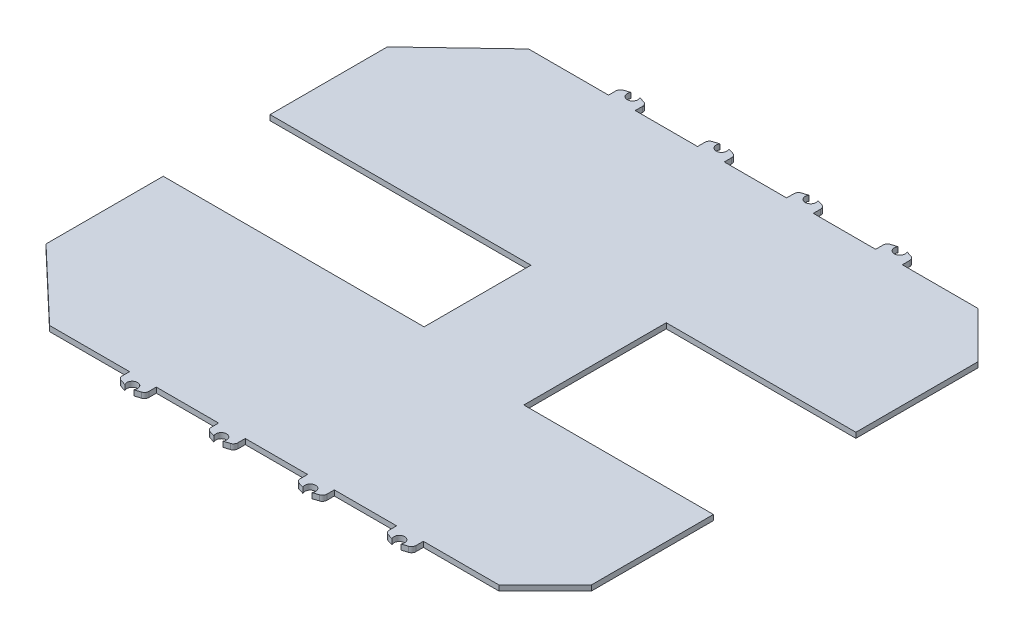
SolidWorks part; units mm, degrees
material "Acrylic (Medium-high impact)"
ref_plane "Front Plane" through (0, 0, 0) normal (0, 0, 1) x (1, 0, 0)
ref_plane "Top Plane" through (0, 0, 0) normal (0, 1, 0) x (1, 0, 0)
ref_plane "Right Plane" through (0, 0, 0) normal (1, 0, 0) x (0, 0, -1)
sketch "Sketch1" plane through (0, 0, 0) normal (0, 1, 0) x (1, 0, 0)
  line L0 (-405.7286, 140) -> (-405.7286, 283.2828) construction
  line L1 (-405.7286, 283.2828) -> (-452, 283.2828) construction
  line L2 (-405.7286, 20) -> (-405.7286, -123.2828) construction
  line L3 (-405.7286, -123.2828) -> (-452, -123.2828) construction
  line L4 (240, 308.3431) -> (157.7738, 308.3431) construction
  line L5 (240, 160) -> (0, 160)
  line L6 (240, 160) -> (240, 0)
  line L7 (240, 0) -> (0, 0)
  line L8 (0, 160) -> (0, 0)
  line L9 (-132, 140) -> (-452, 140)
  line L10 (-132, 140) -> (-132, 20)
  line L11 (-132, 20) -> (-452, 20)
  line L12 (-452, 140) -> (-452, 20)
  line L13 (157.7738, 308.3431) -> (157.7738, 160) construction
  line L14 (-452, 283.2828) -> (-452, -123.2828) construction
  line L15 (-452, -123.2828) -> (-354.4029, -216) construction
  line L16 (-354.4029, -216) -> (172.3431, -216) construction
  line L17 (172.3431, -216) -> (240, -148.3431) construction
  line L18 (240, -148.3431) -> (240, 308.3431) construction
  line L19 (240, 308.3431) -> (172.3431, 376) construction
  line L20 (172.3431, 376) -> (-354.4029, 376) construction
  line L21 (-354.4029, 376) -> (-452, 283.2828) construction
  line L22 (172.3431, 0) -> (172.3431, -148.3431) construction
  line L23 (172.3431, -148.3431) -> (240, -148.3431) construction
  line L24 (-425, 271.6913) -> (-425, -111.6913)
  line L25 (-425, -111.6913) -> (-343.6225, -189)
  line L26 (-343.6225, -189) -> (161.1594, -189)
  line L27 (161.1594, -189) -> (213, -137.1594)
  line L28 (213, -137.1594) -> (213, 297.1594)
  line L29 (213, 297.1594) -> (161.1594, 349)
  line L30 (161.1594, 349) -> (-343.6225, 349)
  line L31 (-343.6225, 349) -> (-425, 271.6913)
  line L32 (61.1594, 361) -> (61.1594, 349) construction
  line L33 (46.1594, 349) -> (46.1594, 357.3477)
  line L34 (49.6387, 362.1108) -> (57.8225, 364.7236)
  line L35 (72.6801, 362.1108) -> (64.4963, 364.7236)
  line L36 (76.1594, 349) -> (76.1594, 357.3477)
  line L37 (56.0594, 364.1607) -> (56.0594, 359.532) construction
  circle A0 centre (61.1594, 361) radius 5
  arc A1 (46.1594, 357.3477) -> (49.6387, 362.1108) centre (51.1594, 357.3477) cw
  arc A2 (76.1594, 357.3477) -> (72.6801, 362.1108) centre (71.1594, 357.3477) ccw
  circle A3 centre (61.1594, 361) radius 6
  point P41 (46.1594, 361)
  point P47 (56.0594, 364.1607)
  point P48 (57.6964, 364.6067)
  dimension "D11" = 10
  dimension "D16" = 5
  dimension "D18" = 12
  dimension "D1" = 120
  dimension "D2" = 320
  dimension "D3" = 160
  dimension "D4" = 240
  dimension "D5" = 526.746
  dimension "D6" = 95.6812
  dimension "D7" = 456.6863
  dimension "D8" = 67.6569
  dimension "D9" = 97.5971
  dimension "D10" = 406.5655
  dimension "D12" = 12
  dimension "D13" = 100
  dimension "D14" = 12
  dimension "D15" = 15
  dimension "D17" = 27
  dimension "D19" = 5.1
extrude "Boss-Extrude1" add sketch "Sketch1" along normal blind 6 contours L30 L31 L24 L9 L10 L11 L25 L26 L27 L28 L7 L8 L5 L29 region at (-106.5717, 0, -80)
extrude "Boss-Extrude2" add sketch "Sketch1<3>" along normal blind 6 contours A3 L34 A1 L33 L30 L36 A2 L35 region at (61.1594, 0, -354.9095)
sketch "Sketch1<3>" plane through (0, 0, 0) normal (0, 1, 0) x (1, 0, 0) same geometry as "Sketch1"
pattern_linear "LPattern1" count 4 spacing 100 along (-1, 0, 0) of "Boss-Extrude2"
ref_plane "Plane1" through (0, 0, -80) normal (0, 0, 1) x (1, 0, 0)
mirror "Mirror1" about plane through (0, 0, -80) normal (0, 0, 1) of "Boss-Extrude2", "LPattern1"
